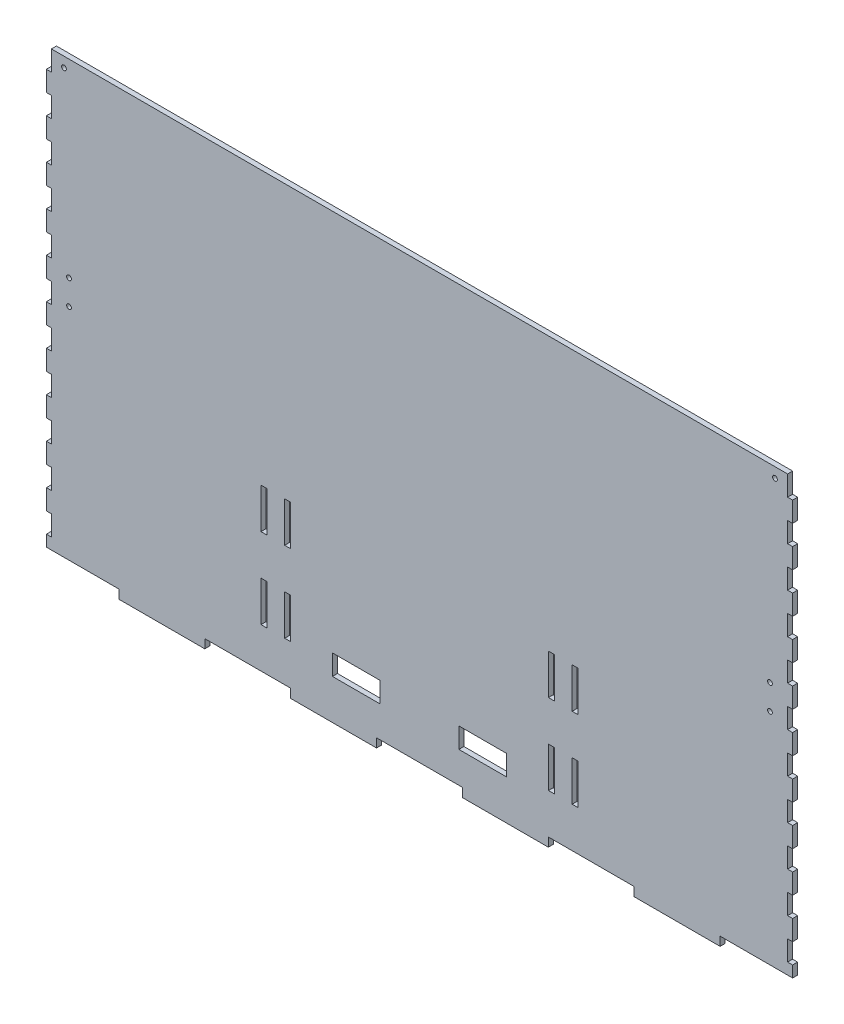
SolidWorks part; units mm, degrees
ref_plane "Front Plane" through (0, 0, 0) normal (0, 0, 1) x (1, 0, 0)
ref_plane "Top Plane" through (0, 0, 0) normal (0, 1, 0) x (1, 0, 0)
ref_plane "Right Plane" through (0, 0, 0) normal (1, 0, 0) x (0, 0, -1)
sketch "Sketch1" plane through (0, 0, 0) normal (0, 0, 1) x (1, 0, 0)
  line L0 (0, 139.7) -> (0, -139.7) construction
  line L1 (-406.4, 139.7) -> (406.4, 139.7)
  line L2 (-406.4, 139.7) -> (-406.4, -139.7)
  line L3 (-406.4, -139.7) -> (406.4, -139.7)
  line L4 (406.4, 139.7) -> (406.4, -139.7)
  line L49 (-381, 127) -> (-381, 114.3)
  line L54 (-381, 139.7) -> (-377.825, 139.7)
  line L55 (-381, 139.7) -> (-381, 127)
  line L56 (-381, 127) -> (-377.825, 127)
  line L57 (-377.825, 139.7) -> (-377.825, 127)
  line L58 (-381, 127) -> (-377.825, 127)
  line L59 (-377.825, 127) -> (-377.825, 114.3)
  line L60 (-381, 114.3) -> (-377.825, 114.3)
  line L61 (-381, 114.3) -> (-381, 101.6)
  line L62 (-381, 114.3) -> (-377.825, 114.3)
  line L63 (-377.825, 114.3) -> (-377.825, 101.6)
  line L64 (-381, 101.6) -> (-377.825, 101.6)
  line L65 (-381, 101.6) -> (-381, 88.9)
  line L66 (-381, 101.6) -> (-377.825, 101.6)
  line L67 (-377.825, 101.6) -> (-377.825, 88.9)
  line L68 (-381, 88.9) -> (-377.825, 88.9)
  line L69 (-381, 88.9) -> (-381, 76.2)
  line L70 (-381, 88.9) -> (-377.825, 88.9)
  line L71 (-377.825, 88.9) -> (-377.825, 76.2)
  line L72 (-381, 76.2) -> (-377.825, 76.2)
  line L73 (-381, 76.2) -> (-381, 63.5)
  line L74 (-381, 76.2) -> (-377.825, 76.2)
  line L75 (-377.825, 76.2) -> (-377.825, 63.5)
  line L76 (-381, 63.5) -> (-377.825, 63.5)
  line L77 (-381, 63.5) -> (-381, 50.8)
  line L78 (-381, 63.5) -> (-377.825, 63.5)
  line L79 (-377.825, 63.5) -> (-377.825, 50.8)
  line L80 (-381, 50.8) -> (-377.825, 50.8)
  line L81 (-381, 50.8) -> (-381, 38.1)
  line L82 (-381, 50.8) -> (-377.825, 50.8)
  line L83 (-377.825, 50.8) -> (-377.825, 38.1)
  line L84 (-381, 38.1) -> (-377.825, 38.1)
  line L85 (-381, 38.1) -> (-381, 25.4)
  line L86 (-381, 38.1) -> (-377.825, 38.1)
  line L87 (-377.825, 38.1) -> (-377.825, 25.4)
  line L88 (-381, 25.4) -> (-377.825, 25.4)
  line L89 (377.825, 127) -> (377.825, 114.3)
  line L90 (377.825, 139.7) -> (381, 139.7)
  line L91 (377.825, 139.7) -> (377.825, 127)
  line L92 (377.825, 127) -> (381, 127)
  line L93 (381, 139.7) -> (381, 127)
  line L94 (377.825, 127) -> (381, 127)
  line L95 (381, 127) -> (381, 114.3)
  line L96 (377.825, 114.3) -> (381, 114.3)
  line L97 (377.825, 114.3) -> (377.825, 101.6)
  line L98 (377.825, 114.3) -> (381, 114.3)
  line L99 (381, 114.3) -> (381, 101.6)
  line L100 (377.825, 101.6) -> (381, 101.6)
  line L101 (377.825, 101.6) -> (377.825, 88.9)
  line L102 (377.825, 101.6) -> (381, 101.6)
  line L103 (381, 101.6) -> (381, 88.9)
  line L104 (377.825, 88.9) -> (381, 88.9)
  line L105 (377.825, 88.9) -> (377.825, 76.2)
  line L106 (377.825, 88.9) -> (381, 88.9)
  line L107 (381, 88.9) -> (381, 76.2)
  line L108 (377.825, 76.2) -> (381, 76.2)
  line L109 (377.825, 76.2) -> (377.825, 63.5)
  line L110 (377.825, 76.2) -> (381, 76.2)
  line L111 (381, 76.2) -> (381, 63.5)
  line L112 (377.825, 63.5) -> (381, 63.5)
  line L113 (377.825, 63.5) -> (377.825, 50.8)
  line L114 (377.825, 63.5) -> (381, 63.5)
  line L115 (381, 63.5) -> (381, 50.8)
  line L116 (377.825, 50.8) -> (381, 50.8)
  line L117 (377.825, 50.8) -> (377.825, 38.1)
  line L118 (377.825, 50.8) -> (381, 50.8)
  line L119 (381, 50.8) -> (381, 38.1)
  line L120 (377.825, 38.1) -> (381, 38.1)
  line L121 (377.825, 38.1) -> (377.825, 25.4)
  line L122 (377.825, 38.1) -> (381, 38.1)
  line L123 (381, 38.1) -> (381, 25.4)
  line L124 (377.825, 25.4) -> (381, 25.4)
  line L125 (-352.2133, -134.112) -> (-352.2133, -139.7)
  line L126 (-406.4, -134.112) -> (-352.2133, -134.112)
  line L127 (-406.4, -134.112) -> (-406.4, -139.7)
  line L128 (-406.4, -139.7) -> (-352.2133, -139.7)
  line L129 (-352.2133, -134.112) -> (-352.2133, -139.7)
  line L130 (-352.2133, -134.112) -> (-298.0267, -134.112)
  line L131 (-298.0267, -134.112) -> (-298.0267, -139.7)
  line L132 (-352.2133, -139.7) -> (-298.0267, -139.7)
  line L133 (-298.0267, -134.112) -> (-298.0267, -139.7)
  line L134 (-298.0267, -134.112) -> (-243.84, -134.112)
  line L135 (-243.84, -134.112) -> (-243.84, -139.7)
  line L136 (-298.0267, -139.7) -> (-243.84, -139.7)
  line L137 (-243.84, -134.112) -> (-243.84, -139.7)
  line L138 (-243.84, -134.112) -> (-189.6533, -134.112)
  line L139 (-189.6533, -134.112) -> (-189.6533, -139.7)
  line L140 (-243.84, -139.7) -> (-189.6533, -139.7)
  line L141 (-189.6533, -134.112) -> (-189.6533, -139.7)
  line L142 (-189.6533, -134.112) -> (-135.4667, -134.112)
  line L143 (-135.4667, -134.112) -> (-135.4667, -139.7)
  line L144 (-189.6533, -139.7) -> (-135.4667, -139.7)
  line L145 (-135.4667, -134.112) -> (-135.4667, -139.7)
  line L146 (-135.4667, -134.112) -> (-81.28, -134.112)
  line L147 (-81.28, -134.112) -> (-81.28, -139.7)
  line L148 (-135.4667, -139.7) -> (-81.28, -139.7)
  line L149 (-81.28, -134.112) -> (-81.28, -139.7)
  line L150 (-81.28, -134.112) -> (-27.0933, -134.112)
  line L151 (-27.0933, -134.112) -> (-27.0933, -139.7)
  line L152 (-81.28, -139.7) -> (-27.0933, -139.7)
  line L153 (-27.0933, -134.112) -> (-27.0933, -139.7)
  line L154 (-27.0933, -134.112) -> (27.0933, -134.112)
  line L155 (27.0933, -134.112) -> (27.0933, -139.7)
  line L156 (-27.0933, -139.7) -> (27.0933, -139.7)
  line L157 (27.0933, -134.112) -> (27.0933, -139.7)
  line L158 (27.0933, -134.112) -> (81.28, -134.112)
  line L159 (81.28, -134.112) -> (81.28, -139.7)
  line L160 (27.0933, -139.7) -> (81.28, -139.7)
  line L161 (81.28, -134.112) -> (81.28, -139.7)
  line L162 (81.28, -134.112) -> (135.4667, -134.112)
  line L163 (135.4667, -134.112) -> (135.4667, -139.7)
  line L164 (81.28, -139.7) -> (135.4667, -139.7)
  line L165 (135.4667, -134.112) -> (135.4667, -139.7)
  line L166 (135.4667, -134.112) -> (189.6533, -134.112)
  line L167 (189.6533, -134.112) -> (189.6533, -139.7)
  line L168 (135.4667, -139.7) -> (189.6533, -139.7)
  line L169 (189.6533, -134.112) -> (189.6533, -139.7)
  line L170 (189.6533, -134.112) -> (243.84, -134.112)
  line L171 (243.84, -134.112) -> (243.84, -139.7)
  line L172 (189.6533, -139.7) -> (243.84, -139.7)
  line L173 (243.84, -134.112) -> (243.84, -139.7)
  line L174 (243.84, -134.112) -> (298.0267, -134.112)
  line L175 (298.0267, -134.112) -> (298.0267, -139.7)
  line L176 (243.84, -139.7) -> (298.0267, -139.7)
  line L177 (298.0267, -134.112) -> (298.0267, -139.7)
  line L178 (298.0267, -134.112) -> (352.2133, -134.112)
  line L179 (352.2133, -134.112) -> (352.2133, -139.7)
  line L180 (298.0267, -139.7) -> (352.2133, -139.7)
  line L181 (352.2133, -134.112) -> (352.2133, -139.7)
  line L182 (352.2133, -134.112) -> (406.4, -134.112)
  line L183 (406.4, -134.112) -> (406.4, -139.7)
  line L184 (352.2133, -139.7) -> (406.4, -139.7)
  line L205 (-90.678, 84.5227) -> (-90.678, -139.7) construction
  line L206 (90.678, 84.5227) -> (90.678, -139.7) construction
  line L207 (-90.678, -27.5886) -> (90.678, -27.5886) construction
  line L208 (-381, 25.4) -> (-381, 12.7)
  line L209 (-381, 25.4) -> (-377.825, 25.4)
  line L210 (-377.825, 25.4) -> (-377.825, 12.7)
  line L211 (-381, 12.7) -> (-377.825, 12.7)
  line L212 (-381, 12.7) -> (-381, 0)
  line L213 (-381, 12.7) -> (-377.825, 12.7)
  line L214 (-377.825, 12.7) -> (-377.825, 0)
  line L215 (-381, 0) -> (-377.825, 0)
  line L224 (-377.825, 0) -> (377.825, 0) construction
  line L229 (377.825, 25.4) -> (377.825, 12.7)
  line L230 (377.825, 25.4) -> (381, 25.4)
  line L231 (381, 25.4) -> (381, 12.7)
  line L232 (377.825, 12.7) -> (381, 12.7)
  line L233 (377.825, 12.7) -> (377.825, 0)
  line L234 (377.825, 12.7) -> (381, 12.7)
  line L235 (381, 12.7) -> (381, 0)
  line L236 (377.825, 0) -> (381, 0)
  line L237 (-381, 0) -> (-381, -12.7)
  line L238 (-381, 0) -> (-377.825, 0)
  line L239 (-377.825, 0) -> (-377.825, -12.7)
  line L240 (-381, -12.7) -> (-377.825, -12.7)
  line L241 (-381, -12.7) -> (-381, -25.4)
  line L242 (-381, -12.7) -> (-377.825, -12.7)
  line L243 (-377.825, -12.7) -> (-377.825, -25.4)
  line L244 (-381, -25.4) -> (-377.825, -25.4)
  line L245 (-381, -25.4) -> (-381, -38.1)
  line L246 (-381, -25.4) -> (-377.825, -25.4)
  line L247 (-377.825, -25.4) -> (-377.825, -38.1)
  line L248 (-381, -38.1) -> (-377.825, -38.1)
  line L249 (-381, -38.1) -> (-381, -50.8)
  line L250 (-381, -38.1) -> (-377.825, -38.1)
  line L251 (-377.825, -38.1) -> (-377.825, -50.8)
  line L252 (-381, -50.8) -> (-377.825, -50.8)
  line L253 (-381, -50.8) -> (-381, -63.5)
  line L254 (-381, -50.8) -> (-377.825, -50.8)
  line L255 (-377.825, -50.8) -> (-377.825, -63.5)
  line L256 (-381, -63.5) -> (-377.825, -63.5)
  line L257 (-381, -63.5) -> (-381, -76.2)
  line L258 (-381, -63.5) -> (-377.825, -63.5)
  line L259 (-377.825, -63.5) -> (-377.825, -76.2)
  line L260 (-381, -76.2) -> (-377.825, -76.2)
  line L261 (-381, -76.2) -> (-381, -88.9)
  line L262 (-381, -76.2) -> (-377.825, -76.2)
  line L263 (-377.825, -76.2) -> (-377.825, -88.9)
  line L264 (-381, -88.9) -> (-377.825, -88.9)
  line L265 (-381, -88.9) -> (-381, -101.6)
  line L266 (-381, -88.9) -> (-377.825, -88.9)
  line L267 (-377.825, -88.9) -> (-377.825, -101.6)
  line L268 (-381, -101.6) -> (-377.825, -101.6)
  line L269 (-381, -101.6) -> (-381, -114.3)
  line L270 (-381, -101.6) -> (-377.825, -101.6)
  line L271 (-377.825, -101.6) -> (-377.825, -114.3)
  line L272 (-381, -114.3) -> (-377.825, -114.3)
  line L273 (-381, -114.3) -> (-381, -127)
  line L274 (-381, -114.3) -> (-377.825, -114.3)
  line L275 (-377.825, -114.3) -> (-377.825, -127)
  line L276 (-381, -127) -> (-377.825, -127)
  line L277 (-381, -127) -> (-381, -139.7)
  line L278 (-381, -127) -> (-377.825, -127)
  line L279 (-377.825, -127) -> (-377.825, -139.7)
  line L280 (-381, -139.7) -> (-377.825, -139.7)
  line L281 (377.825, 0) -> (377.825, -12.7)
  line L282 (377.825, 0) -> (381, 0)
  line L283 (381, 0) -> (381, -12.7)
  line L284 (377.825, -12.7) -> (381, -12.7)
  line L285 (377.825, -12.7) -> (377.825, -25.4)
  line L286 (377.825, -12.7) -> (381, -12.7)
  line L287 (381, -12.7) -> (381, -25.4)
  line L288 (377.825, -25.4) -> (381, -25.4)
  line L289 (377.825, -25.4) -> (377.825, -38.1)
  line L290 (377.825, -25.4) -> (381, -25.4)
  line L291 (381, -25.4) -> (381, -38.1)
  line L292 (377.825, -38.1) -> (381, -38.1)
  line L293 (377.825, -38.1) -> (377.825, -50.8)
  line L294 (377.825, -38.1) -> (381, -38.1)
  line L295 (381, -38.1) -> (381, -50.8)
  line L296 (377.825, -50.8) -> (381, -50.8)
  line L297 (377.825, -50.8) -> (377.825, -63.5)
  line L298 (377.825, -50.8) -> (381, -50.8)
  line L299 (381, -50.8) -> (381, -63.5)
  line L300 (377.825, -63.5) -> (381, -63.5)
  line L301 (377.825, -63.5) -> (377.825, -76.2)
  line L302 (377.825, -63.5) -> (381, -63.5)
  line L303 (381, -63.5) -> (381, -76.2)
  line L304 (377.825, -76.2) -> (381, -76.2)
  line L305 (377.825, -76.2) -> (377.825, -88.9)
  line L306 (377.825, -76.2) -> (381, -76.2)
  line L307 (381, -76.2) -> (381, -88.9)
  line L308 (377.825, -88.9) -> (381, -88.9)
  line L309 (377.825, -88.9) -> (377.825, -101.6)
  line L310 (377.825, -88.9) -> (381, -88.9)
  line L311 (381, -88.9) -> (381, -101.6)
  line L312 (377.825, -101.6) -> (381, -101.6)
  line L313 (377.825, -101.6) -> (377.825, -114.3)
  line L314 (377.825, -101.6) -> (381, -101.6)
  line L315 (381, -101.6) -> (381, -114.3)
  line L316 (377.825, -114.3) -> (381, -114.3)
  line L317 (377.825, -114.3) -> (377.825, -127)
  line L318 (377.825, -114.3) -> (381, -114.3)
  line L319 (381, -114.3) -> (381, -127)
  line L320 (377.825, -127) -> (381, -127)
  line L321 (377.825, -127) -> (377.825, -139.7)
  line L322 (377.825, -127) -> (381, -127)
  line L323 (381, -127) -> (381, -139.7)
  line L324 (377.825, -139.7) -> (381, -139.7)
  point P6 (0, 0)
  point P128 (0, -27.5886)
  point P153 (0, 0)
  dimension "D4" = 12.7
  dimension "D5" = 3.175
  dimension "D10" = 181.356
  dimension "D12" = 755.65
  dimension "D8" = 812.8
  dimension "D11" = 54.1867
  dimension "D2" = 273.812
  dimension "D9" = 279.4
  dimension "D3" = 22
  dimension "D7" = 15
  dimension "D6" = 22
extrude "Main Extrude" add sketch "Sketch1" along normal blind 3.175 contours L321 L317 L313 L309 L305 L301 L297 L293 L289 L285 L281 L233 L229 L121 L117 L113 L109 L105 L101 L97 L89 L91 L1 L57 L59 L63 L67 L71 L75 L79 L83 L87 L210 L214 L239 L243 L247 L251 L255 L259 L263 L267 L271 L275 L279 L126 L130 L134 L138 L142 L146 | L277 L273 L269 L265 L261 L257 L253 L249 L245 L241 L237 L212 L208 L85 L81 L77 L73 L69 L65 L61 L49 L55 L1 L2 L126 | L319 L323 L182 L4 L1 L93 L95 L99 L103 L107 L111 L115 L119 L123 L231 L235 L283 L287 L291 L295 L299 L303 L307 L311 L315 | L126 L279 L3 L125 | L135 L134 L131 L3 | L143 L142 L139 L3 | L151 L150 L147 L3 | L159 L158 L155 L3 | L167 L166 L163 L3 | L175 L174 L171 L3 | L323 L182 L321 L184 | L89 L96 L95 L92 | L101 L104 L103 L100 | L109 L112 L111 L108 | L117 L120 L119 L116 | L229 L232 L231 L124 | L281 L284 L283 L236 | L289 L292 L291 L288 | L297 L300 L299 L296 | L305 L308 L307 L304 | L313 L316 L315 L312 | L323 L320 L321 L182 | L49 L60 L59 L56 | L65 L68 L67 L64 | L73 L76 L75 L72 | L81 L84 L83 L80 | L208 L211 L210 L88 | L237 L240 L239 L215 | L245 L248 L247 L244 | L253 L256 L255 L252 | L261 L264 L263 L260 | L269 L272 L271 L268 | L279 L276 L277 L126 | L277 L126 L2 L3 | L321 L182 L179 L3 | L182 L323 L3 L4 | L279 L126 L277 L128 region at (-393.7, 2.794, 0) region at (-393.7, -136.906, 0) region at (0, 2.794, 0) region at (-379.4125, 120.65, 0) region at (-379.4125, -130.556, 0) region at (-379.4125, -136.906, 0) region at (-365.0192, -136.906, 0) region at (393.7, 2.794, 0) region at (379.4125, 120.65, 0) region at (-379.4125, 95.25, 0) region at (-379.4125, -107.95, 0) region at (-270.9333, -136.906, 0) region at (393.7, -136.906, 0) region at (379.4125, 95.25, 0) region at (-379.4125, 69.85, 0) region at (-379.4125, -82.55, 0) region at (379.4125, -136.906, 0) region at (379.4125, -130.556, 0) region at (-162.56, -136.906, 0) region at (365.0192, -136.906, 0) region at (379.4125, 69.85, 0) region at (-379.4125, 44.45, 0) region at (-379.4125, -57.15, 0) region at (379.4125, -107.95, 0) region at (-54.1867, -136.906, 0) region at (270.9333, -136.906, 0) region at (379.4125, 44.45, 0) region at (-379.4125, 19.05, 0) region at (-379.4125, -31.75, 0) region at (379.4125, -82.55, 0) region at (54.1867, -136.906, 0) region at (162.56, -136.906, 0) region at (379.4125, 19.05, 0) region at (-379.4125, -6.35, 0) region at (379.4125, -57.15, 0) region at (379.4125, -6.35, 0) region at (379.4125, -31.75, 0)
sketch "Sketch8" plane through (0, 0, 3.175) normal (0, 0, 1) x (1, 0, 0)
  line L0 (-406.4, 139.7) -> (-406.4, -139.7) construction
  line L1 (-381, 28.2575) -> (-384.175, 28.2575)
  line L2 (-381, 28.2575) -> (-381, -3.6195)
  line L3 (-381, -3.6195) -> (-384.175, -3.6195)
  line L4 (-384.175, 28.2575) -> (-384.175, -3.6195)
  line L5 (-406.4, -139.7) -> (-352.2133, -139.7) construction
  line L6 (381, 28.2575) -> (384.175, 28.2575)
  line L7 (381, 28.2575) -> (381, -3.6195)
  line L8 (381, -3.6195) -> (384.175, -3.6195)
  line L9 (384.175, 28.2575) -> (384.175, -3.6195)
  line L11 (-381, 88.9) -> (-381, 76.2) construction
  line L12 (-352.2133, -134.112) -> (-298.0267, -134.112) construction
  line L13 (381, 88.9) -> (381, 76.2) construction
  line L14 (-393.7, -120.65) -> (393.7, -120.65) construction
  circle A0 centre (-393.7, -120.65) radius 1.5
  circle A1 centre (393.7, -120.65) radius 1.5
  point P6 (0, -120.65)
  point P16 (-384.175, 12.319)
  dimension "D5" = 3
  dimension "D1" = 31.877
  dimension "D2" = 3.175
  dimension "D3" = 146.431
  dimension "D4" = 19.05
  dimension "D6" = 12.7
extrude "Mount Holes" cut sketch "Sketch8" against normal through all
sketch "Sketch3" plane through (0, 0, 3.175) normal (0, 0, 1) x (1, 0, 0)
  line L0 (-135.4667, -134.112) -> (-81.28, -134.112) construction
  line L1 (-96.52, 126.492) -> (-84.836, 126.492)
  line L2 (-96.52, 126.492) -> (-96.52, -134.112)
  line L3 (-96.52, -134.112) -> (-84.836, -134.112)
  line L4 (-84.836, 126.492) -> (-84.836, -134.112)
  line L5 (81.28, -134.112) -> (135.4667, -134.112) construction
  line L6 (84.836, 126.492) -> (96.52, 126.492)
  line L7 (84.836, 126.492) -> (84.836, -134.112)
  line L8 (84.836, -134.112) -> (96.52, -134.112)
  line L9 (96.52, 126.492) -> (96.52, -134.112)
  line L10 (-84.836, -3.81) -> (84.836, -3.81) construction
  line L12 (-106.553, 10.3505) -> (-74.803, 10.3505)
  line L13 (-106.553, 10.3505) -> (-106.553, 0.8255)
  line L14 (-106.553, 0.8255) -> (-74.803, 0.8255)
  line L15 (-74.803, 10.3505) -> (-74.803, 0.8255)
  line L16 (74.803, 10.3505) -> (106.553, 10.3505)
  line L17 (74.803, 10.3505) -> (74.803, 0.8255)
  line L18 (74.803, 0.8255) -> (106.553, 0.8255)
  line L19 (106.553, 10.3505) -> (106.553, 0.8255)
  line L20 (-96.52, 126.492) -> (-92.6465, 126.492)
  line L21 (-96.52, 126.492) -> (-96.52, 82.042)
  line L22 (-96.52, 82.042) -> (-92.6465, 82.042)
  line L23 (-92.6465, 126.492) -> (-92.6465, 82.042)
  line L24 (-84.836, 126.492) -> (-88.7095, 126.492)
  line L25 (-84.836, 126.492) -> (-84.836, 82.042)
  line L26 (-84.836, 82.042) -> (-88.7095, 82.042)
  line L27 (-88.7095, 126.492) -> (-88.7095, 82.042)
  line L28 (84.836, 126.492) -> (88.7095, 126.492)
  line L29 (84.836, 126.492) -> (84.836, 82.042)
  line L30 (84.836, 82.042) -> (88.7095, 82.042)
  line L31 (88.7095, 126.492) -> (88.7095, 82.042)
  line L32 (96.52, 126.492) -> (92.6465, 126.492)
  line L33 (96.52, 126.492) -> (96.52, 82.042)
  line L34 (96.52, 82.042) -> (92.6465, 82.042)
  line L35 (92.6465, 126.492) -> (92.6465, 82.042)
  point P14 (-90.678, 126.492)
  point P15 (90.678, 126.492)
  point P16 (0, -3.81)
  point P27 (-90.678, 10.3505)
  point P28 (90.678, 10.3505)
  point P29 (-74.803, 5.588)
  dimension "D1" = 11.684
  dimension "D2" = 260.604
  dimension "D3" = 181.356
  dimension "D4" = 9.525
  dimension "D5" = 139.7
  dimension "D6" = 31.75
  dimension "D8" = 3.937
  dimension "D7" = 44.45
extrude "Door Slots" [suppressed] cut sketch "Sketch3" against normal through all contours L2 L12 L4 L1 | L2 L14 L4 L12 | L15 L12 L4 L14 | L13 L14 L2 L12 | L14 L2 L3 L4 | L7 L16 L9 L6 | L7 L18 L9 L16 | L19 L16 L9 L18 | L17 L18 L7 L16 | L18 L7 L8 L9
sketch "Sketch4" plane through (0, 0, 0) normal (0, 0, 1) x (1, 0, 0)
  line L1 (-81.28, -139.7) -> (-27.0933, -139.7) construction
  line L2 (-55.88, -112.41) -> (-52.578, -112.41)
  line L3 (-52.578, -112.41) -> (-52.578, -106.172)
  line L4 (-52.578, -106.172) -> (-1.778, -106.172)
  line L5 (-1.778, -106.172) -> (-1.778, -112.41)
  line L6 (-1.778, -112.41) -> (1.524, -112.41)
  line L9 (-55.88, -112.41) -> (-55.88, -134.112)
  line L10 (-55.88, -134.112) -> (-52.578, -134.112)
  line L11 (-52.578, -134.112) -> (-52.578, -139.7)
  line L12 (1.524, -112.41) -> (1.524, -134.112)
  line L13 (1.524, -134.112) -> (-1.778, -134.112)
  line L14 (-1.778, -134.112) -> (-1.778, -139.7)
  line L15 (-52.578, -139.7) -> (-1.778, -139.7)
  line L16 (-27.0933, -134.112) -> (27.0933, -134.112) construction
  line L17 (-27.0933, -134.112) -> (27.0933, -134.112) construction
  line L18 (12.128, -101.642) -> (42.228, -101.642)
  line L19 (12.128, -101.642) -> (12.128, -114.492)
  line L20 (12.128, -114.492) -> (42.228, -114.492)
  line L21 (42.228, -101.642) -> (42.228, -114.492)
  line L24 (-96.52, -134.112) -> (-84.836, -134.112) construction
  line L25 (84.836, -134.112) -> (96.52, -134.112) construction
  point P9 (-27.178, -106.172)
  point P10 (-27.178, -139.7)
  point P22 (27.178, -114.492)
  point P25 (90.678, -134.112)
  point P26 (12.128, -108.067)
  point P30 (-90.678, -134.112)
  dimension "D1" = 50.8
  dimension "D2" = 3.302
  dimension "D4" = 21.702
  dimension "D5" = 30.1
  dimension "D6" = 12.85
  dimension "D9" = 63.5
  dimension "D8" = 63.5
  dimension "D3" = 27.94
  dimension "D7" = 26.045
extrude "Trough and Lever Holes" [suppressed] cut sketch "Sketch4" along normal through all contours L11 L15 L14 L13 L12 L6 L5 L4 L3 L2 L9 L10 | L21 L18 L19 L20
sketch "Sketch5" plane through (0, 0, 3.175) normal (0, 0, 1) x (1, 0, 0)
  line L0 (-90.678, 126.492) -> (-90.678, -134.112) construction
  line L1 (-96.52, 126.492) -> (-84.836, 126.492) construction
  line L2 (-96.52, -134.112) -> (-84.836, -134.112) construction
  line L3 (90.678, 126.492) -> (90.678, -134.112) construction
  line L4 (84.836, 126.492) -> (96.52, 126.492) construction
  line L5 (84.836, -134.112) -> (96.52, -134.112) construction
  line L6 (-135.4667, -134.112) -> (-81.28, -134.112) construction
  line L19 (-99.998, -134.112) -> (-96.3199, -134.112)
  line L20 (-99.998, -134.112) -> (-99.998, -108.712)
  line L21 (-99.998, -108.712) -> (-96.3199, -108.712)
  line L22 (-96.3199, -134.112) -> (-96.3199, -108.712)
  line L24 (-99.998, -108.712) -> (-96.3199, -108.712)
  line L25 (-99.998, -108.712) -> (-99.998, -83.312)
  line L26 (-99.998, -83.312) -> (-96.3199, -83.312)
  line L27 (-96.3199, -108.712) -> (-96.3199, -83.312)
  line L28 (-96.3199, -83.312) -> (-99.998, -83.312)
  line L29 (-96.3199, -83.312) -> (-96.3199, -57.912)
  line L30 (-96.3199, -57.912) -> (-99.998, -57.912)
  line L31 (-99.998, -83.312) -> (-99.998, -57.912)
  line L32 (-99.998, -57.912) -> (-96.3199, -57.912)
  line L33 (-99.998, -57.912) -> (-99.998, -32.512)
  line L34 (-99.998, -32.512) -> (-96.3199, -32.512)
  line L35 (-96.3199, -57.912) -> (-96.3199, -32.512)
  line L36 (-96.3199, -32.512) -> (-99.998, -32.512)
  line L37 (-96.3199, -32.512) -> (-96.3199, -7.112)
  line L38 (-96.3199, -7.112) -> (-99.998, -7.112)
  line L39 (-99.998, -32.512) -> (-99.998, -7.112)
  line L40 (-81.358, -108.712) -> (-85.0361, -108.712)
  line L41 (-85.0361, -134.112) -> (-85.0361, -108.712)
  line L42 (-81.358, -134.112) -> (-85.0361, -134.112)
  line L43 (-81.358, -134.112) -> (-81.358, -108.712)
  line L44 (-81.358, -83.312) -> (-85.0361, -83.312)
  line L45 (-85.0361, -108.712) -> (-85.0361, -83.312)
  line L46 (-81.358, -108.712) -> (-85.0361, -108.712)
  line L47 (-81.358, -108.712) -> (-81.358, -83.312)
  line L48 (-85.0361, -57.912) -> (-81.358, -57.912)
  line L49 (-81.358, -83.312) -> (-81.358, -57.912)
  line L50 (-85.0361, -83.312) -> (-81.358, -83.312)
  line L51 (-85.0361, -83.312) -> (-85.0361, -57.912)
  line L52 (-81.358, -32.512) -> (-85.0361, -32.512)
  line L53 (-85.0361, -57.912) -> (-85.0361, -32.512)
  line L54 (-81.358, -57.912) -> (-85.0361, -57.912)
  line L55 (-81.358, -57.912) -> (-81.358, -32.512)
  line L56 (-85.0361, -7.112) -> (-81.358, -7.112)
  line L57 (-81.358, -32.512) -> (-81.358, -7.112)
  line L58 (-85.0361, -32.512) -> (-81.358, -32.512)
  line L59 (-85.0361, -32.512) -> (-85.0361, -7.112)
  line L60 (0, -1.7463) -> (0, 1.7463) construction
  line L61 (99.998, -108.712) -> (96.3199, -108.712)
  line L62 (96.3199, -134.112) -> (96.3199, -108.712)
  line L63 (99.998, -134.112) -> (96.3199, -134.112)
  line L64 (99.998, -134.112) -> (99.998, -108.712)
  line L65 (99.998, -83.312) -> (96.3199, -83.312)
  line L66 (96.3199, -108.712) -> (96.3199, -83.312)
  line L67 (99.998, -108.712) -> (96.3199, -108.712)
  line L68 (99.998, -108.712) -> (99.998, -83.312)
  line L69 (96.3199, -57.912) -> (99.998, -57.912)
  line L70 (99.998, -83.312) -> (99.998, -57.912)
  line L71 (96.3199, -83.312) -> (99.998, -83.312)
  line L72 (96.3199, -83.312) -> (96.3199, -57.912)
  line L73 (99.998, -32.512) -> (96.3199, -32.512)
  line L74 (96.3199, -57.912) -> (96.3199, -32.512)
  line L75 (99.998, -57.912) -> (96.3199, -57.912)
  line L76 (99.998, -57.912) -> (99.998, -32.512)
  line L77 (96.3199, -7.112) -> (99.998, -7.112)
  line L78 (99.998, -32.512) -> (99.998, -7.112)
  line L79 (96.3199, -32.512) -> (99.998, -32.512)
  line L80 (96.3199, -32.512) -> (96.3199, -7.112)
  line L81 (85.0361, -32.512) -> (85.0361, -7.112)
  line L82 (85.0361, -32.512) -> (81.358, -32.512)
  line L83 (81.358, -32.512) -> (81.358, -7.112)
  line L84 (85.0361, -7.112) -> (81.358, -7.112)
  line L85 (81.358, -57.912) -> (81.358, -32.512)
  line L86 (81.358, -57.912) -> (85.0361, -57.912)
  line L87 (85.0361, -57.912) -> (85.0361, -32.512)
  line L88 (81.358, -32.512) -> (85.0361, -32.512)
  line L89 (85.0361, -83.312) -> (85.0361, -57.912)
  line L90 (85.0361, -83.312) -> (81.358, -83.312)
  line L91 (81.358, -83.312) -> (81.358, -57.912)
  line L92 (85.0361, -57.912) -> (81.358, -57.912)
  line L93 (81.358, -108.712) -> (81.358, -83.312)
  line L94 (81.358, -108.712) -> (85.0361, -108.712)
  line L95 (85.0361, -108.712) -> (85.0361, -83.312)
  line L96 (81.358, -83.312) -> (85.0361, -83.312)
  line L97 (81.358, -134.112) -> (81.358, -108.712)
  line L98 (81.358, -134.112) -> (85.0361, -134.112)
  line L99 (85.0361, -134.112) -> (85.0361, -108.712)
  line L100 (81.358, -108.712) -> (85.0361, -108.712)
  dimension "D1" = 25.4
  dimension "D3" = 5.6419
  dimension "D2" = 9.32
extrude "Door Guide Slots" cut sketch "Sketch5" against normal through all contours L21 L27 L26 L25 | L30 L35 L34 L33 | L48 L55 L52 L53 | L40 L47 L44 L45 | L86 L87 L82 L85 | L94 L95 L90 L93 | L69 L76 L73 L74 | L61 L68 L65 L66 region at (-98.1589, -96.012, 3.175) region at (-98.1589, -45.212, 3.175) region at (-83.1971, -96.012, 3.175) region at (-83.1971, -45.212, 3.175) region at (98.1589, -96.012, 3.175) region at (98.1589, -45.212, 3.175) region at (83.1971, -45.212, 3.175) region at (83.1971, -96.012, 3.175)
sketch "Sketch7" plane through (0, 0, 3.175) normal (0, 0, 1) x (1, 0, 0)
  line L0 (-24.828, -108.067) -> (24.828, -108.067) construction
  line L1 (-54.928, -101.642) -> (-24.828, -101.642)
  line L2 (-54.928, -101.642) -> (-54.928, -114.492)
  line L3 (-54.928, -114.492) -> (-24.828, -114.492)
  line L4 (-24.828, -101.642) -> (-24.828, -114.492)
  line L5 (54.928, -101.642) -> (24.828, -101.642)
  line L6 (54.928, -101.642) -> (54.928, -114.492)
  line L7 (54.928, -114.492) -> (24.828, -114.492)
  line L8 (24.828, -101.642) -> (24.828, -114.492)
  line L9 (0, -108.067) -> (0, 0) construction
  line L10 (-96.52, -134.112) -> (-84.836, -134.112) construction
  line L12 (-135.4667, -134.112) -> (-81.28, -134.112) construction
  point P12 (-54.928, -108.067)
  point P15 (-39.878, -101.642)
  point P18 (-90.678, -134.112)
  dimension "D1" = 12.85
  dimension "D2" = 30.1
  dimension "D3" = 50.8
  dimension "D4" = 26.045
extrude "Lever Holes" cut sketch "Sketch7" against normal through all
sketch "Sketch10" [suppressed] plane through (0, 0, 3.175) normal (0, 0, 1) x (1, 0, 0)
  line L0 (-101.678, 127.492) -> (-79.678, 127.492) construction
  line L2 (-92.6465, 126.492) -> (-88.7095, 126.492) construction
  line L3 (-90.678, 127.492) -> (-90.678, 126.492) construction
  line L4 (79.678, 127.492) -> (101.678, 127.492) construction
  line L5 (90.678, 127.492) -> (90.678, 126.492) construction
  line L6 (88.7095, 126.492) -> (92.6465, 126.492) construction
  circle A0 centre (-101.678, 127.492) radius 1.5
  circle A1 centre (-79.678, 127.492) radius 1.5
  circle A2 centre (79.678, 127.492) radius 1.5
  circle A3 centre (101.678, 127.492) radius 1.5
  dimension "D1" = 3
  dimension "D2" = 22
  dimension "D3" = 1
extrude "Door Guide Mount Holes" [suppressed] cut sketch "Sketch10" against normal through all
sketch "Sketch12" plane through (0, 0, 3.175) normal (0, 0, 1) x (1, 0, 0)
  line L0 (-246.507, 20.193) -> (-246.507, 4.445) construction
  line L1 (-221.107, 20.193) -> (-221.107, 4.445) construction
  line L2 (-246.507, 20.193) -> (-221.107, 20.193) construction
  line L3 (-246.507, 4.445) -> (-221.107, 4.445) construction
  line L4 (-243.332, 133.35) -> (-224.282, 133.35) construction
  line L5 (-406.4, 139.7) -> (406.4, 139.7) construction
  line L6 (-233.807, 20.193) -> (-233.807, 133.35) construction
  line L7 (-243.84, -134.112) -> (-189.6533, -134.112) construction
  line L8 (0, -1.7463) -> (0, 1.7463) construction
  line L9 (233.807, 20.193) -> (233.807, 133.35) construction
  line L10 (243.332, 133.35) -> (224.282, 133.35) construction
  line L11 (246.507, 4.445) -> (221.107, 4.445) construction
  line L12 (246.507, 20.193) -> (221.107, 20.193) construction
  line L13 (221.107, 20.193) -> (221.107, 4.445) construction
  line L14 (246.507, 20.193) -> (246.507, 4.445) construction
  circle A0 centre (-246.507, 20.193) radius 1.5
  circle A1 centre (-246.507, 4.445) radius 1.5
  circle A2 centre (-221.107, 4.445) radius 1.5
  circle A3 centre (-221.107, 20.193) radius 1.5
  circle A4 centre (-243.332, 133.35) radius 1.5
  circle A5 centre (-224.282, 133.35) radius 1.5
  circle A6 centre (224.282, 133.35) radius 1.5
  circle A7 centre (243.332, 133.35) radius 1.5
  circle A8 centre (221.107, 20.193) radius 1.5
  circle A9 centre (221.107, 4.445) radius 1.5
  circle A10 centre (246.507, 4.445) radius 1.5
  circle A11 centre (246.507, 20.193) radius 1.5
  point P12 (-233.807, 133.35)
  dimension "D1" = 3
  dimension "D2" = 233.807
  dimension "D3" = 19.05
  dimension "D4" = 6.35
  dimension "D5" = 25.4
  dimension "D6" = 15.748
  dimension "D7" = 138.557
extrude "Extension Clip Holes" cut sketch "Sketch12" against normal through all
sketch "Sketch11" plane through (0, 0, 3.175) normal (0, 0, 1) x (1, 0, 0)
  line L0 (-232.2195, 139.7) -> (-232.2195, 127)
  line L1 (-232.2195, 127) -> (-235.3945, 127)
  line L2 (-235.3945, 127) -> (-235.3945, 114.3)
  line L3 (-235.3945, 114.3) -> (-232.2195, 114.3)
  line L4 (232.2195, 139.7) -> (232.2195, 127)
  line L5 (232.2195, 127) -> (235.3945, 127)
  line L6 (235.3945, 127) -> (235.3945, 114.3)
  line L7 (235.3945, 114.3) -> (232.2195, 114.3)
  line L9 (-381, 127) -> (-377.825, 127) construction
  line L10 (-377.825, 139.7) -> (-377.825, 127) construction
  line L11 (235.3945, 120.65) -> (-235.3945, 120.65) construction
  line L12 (-232.2195, 114.3) -> (-232.2195, 101.6)
  line L13 (-232.2195, 101.6) -> (-235.3945, 101.6)
  line L14 (-235.3945, 101.6) -> (-235.3945, 88.9)
  line L15 (-235.3945, 88.9) -> (-232.2195, 88.9)
  line L16 (232.2195, 114.3) -> (232.2195, 101.6)
  line L17 (232.2195, 101.6) -> (235.3945, 101.6)
  line L18 (235.3945, 101.6) -> (235.3945, 88.9)
  line L19 (235.3945, 88.9) -> (232.2195, 88.9)
  line L20 (-232.2195, 88.9) -> (-232.2195, 76.2)
  line L21 (-232.2195, 76.2) -> (-235.3945, 76.2)
  line L22 (-235.3945, 76.2) -> (-235.3945, 63.5)
  line L23 (-235.3945, 63.5) -> (-232.2195, 63.5)
  line L24 (232.2195, 88.9) -> (232.2195, 76.2)
  line L25 (232.2195, 76.2) -> (235.3945, 76.2)
  line L26 (235.3945, 76.2) -> (235.3945, 63.5)
  line L27 (235.3945, 63.5) -> (232.2195, 63.5)
  line L28 (-232.2195, 63.5) -> (-232.2195, 50.8)
  line L29 (-232.2195, 50.8) -> (-235.3945, 50.8)
  line L30 (-235.3945, 50.8) -> (-235.3945, 38.1)
  line L31 (-235.3945, 38.1) -> (-232.2195, 38.1)
  line L32 (232.2195, 63.5) -> (232.2195, 50.8)
  line L33 (232.2195, 50.8) -> (235.3945, 50.8)
  line L34 (235.3945, 50.8) -> (235.3945, 38.1)
  line L35 (235.3945, 38.1) -> (232.2195, 38.1)
  line L36 (-232.2195, 38.1) -> (-232.2195, 25.4)
  line L37 (-232.2195, 25.4) -> (-235.3945, 25.4)
  line L38 (-235.3945, 25.4) -> (-235.3945, 12.7)
  line L39 (-235.3945, 12.7) -> (-232.2195, 12.7)
  line L40 (232.2195, 38.1) -> (232.2195, 25.4)
  line L41 (232.2195, 25.4) -> (235.3945, 25.4)
  line L42 (235.3945, 25.4) -> (235.3945, 12.7)
  line L43 (235.3945, 12.7) -> (232.2195, 12.7)
  line L44 (-232.2195, 12.7) -> (-232.2195, 0)
  line L45 (-232.2195, 0) -> (-235.3945, 0)
  line L46 (-235.3945, 0) -> (-235.3945, -12.7)
  line L47 (-235.3945, -12.7) -> (-232.2195, -12.7)
  line L48 (232.2195, 12.7) -> (232.2195, 0)
  line L50 (232.2195, 0) -> (235.3945, 0)
  line L52 (235.3945, 0) -> (235.3945, -12.7)
  line L53 (235.3945, -12.7) -> (232.2195, -12.7)
  line L54 (-232.2195, -12.7) -> (-232.2195, -25.4)
  line L55 (-232.2195, -25.4) -> (-235.3945, -25.4)
  line L56 (-235.3945, -25.4) -> (-235.3945, -38.1)
  line L57 (-235.3945, -38.1) -> (-232.2195, -38.1)
  line L58 (232.2195, -12.7) -> (232.2195, -25.4)
  line L59 (232.2195, -25.4) -> (235.3945, -25.4)
  line L60 (235.3945, -25.4) -> (235.3945, -38.1)
  line L61 (235.3945, -38.1) -> (232.2195, -38.1)
  line L62 (-232.2195, -38.1) -> (-232.2195, -50.8)
  line L63 (-232.2195, -50.8) -> (-235.3945, -50.8)
  line L64 (-235.3945, -50.8) -> (-235.3945, -63.5)
  line L65 (-235.3945, -63.5) -> (-232.2195, -63.5)
  line L66 (232.2195, -38.1) -> (232.2195, -50.8)
  line L67 (232.2195, -50.8) -> (235.3945, -50.8)
  line L68 (235.3945, -50.8) -> (235.3945, -63.5)
  line L69 (235.3945, -63.5) -> (232.2195, -63.5)
  line L70 (-232.2195, -63.5) -> (-232.2195, -76.2)
  line L71 (-232.2195, -76.2) -> (-235.3945, -76.2)
  line L72 (-235.3945, -76.2) -> (-235.3945, -88.9)
  line L73 (-235.3945, -88.9) -> (-232.2195, -88.9)
  line L74 (232.2195, -63.5) -> (232.2195, -76.2)
  line L75 (232.2195, -76.2) -> (235.3945, -76.2)
  line L76 (235.3945, -76.2) -> (235.3945, -88.9)
  line L77 (235.3945, -88.9) -> (232.2195, -88.9)
  line L78 (-232.2195, -88.9) -> (-232.2195, -101.6)
  line L79 (-232.2195, -101.6) -> (-235.3945, -101.6)
  line L80 (-235.3945, -101.6) -> (-235.3945, -114.3)
  line L81 (-235.3945, -114.3) -> (-232.2195, -114.3)
  line L82 (232.2195, -88.9) -> (232.2195, -101.6)
  line L83 (232.2195, -101.6) -> (235.3945, -101.6)
  line L84 (235.3945, -101.6) -> (235.3945, -114.3)
  line L85 (235.3945, -114.3) -> (232.2195, -114.3)
  line L86 (-232.2195, -114.3) -> (-232.2195, -127)
  line L87 (-232.2195, -127) -> (-235.3945, -127)
  line L88 (-235.3945, -127) -> (-235.3945, -139.7)
  line L90 (232.2195, -114.3) -> (232.2195, -127)
  line L91 (232.2195, -127) -> (235.3945, -127)
  line L92 (235.3945, -127) -> (235.3945, -139.7)
  line L98 (-406.4, 139.7) -> (406.4, 139.7)
  line L99 (-406.4, 139.7) -> (-406.4, -139.7)
  line L100 (-406.4, -139.7) -> (406.4, -139.7)
  line L101 (406.4, 139.7) -> (406.4, -139.7)
  line L102 (-235.3945, -139.7) -> (-232.2195, -139.7)
  line L103 (235.3945, -139.7) -> (232.2195, -139.7)
  point P14 (-233.807, 127)
  point P15 (233.807, 114.3)
  point P18 (0, 120.65)
  dimension "D2" = 11
  dimension "D1" = 467.614
extrude "Extended Side Cut" [suppressed] cut sketch "Sketch11" against normal through all
extrude "Extension Center Cut" cut sketch "Sketch11<3>" against normal through all contours L99 L100 L39 L31 L23 L15 L2 L1 L98 | L101 L98 L80 L77 L76 L75 L72 L69 L68 L67 L64 L61 L60 L59 L56 L53 L52 L50 L100 region at (-320.0962, 0.0584, 3.175) region at (320.0962, 0.0584, 3.175)
sketch "Sketch11<3>" plane through (0, 0, 3.175) normal (0, 0, 1) x (1, 0, 0) same geometry as "Sketch11"
sketch "Sketch14" [suppressed] plane through (0, 0, 3.175) normal (0, 0, 1) x (1, 0, 0)
  line L1 (-232.2195, 139.7) -> (232.2195, 139.7)
  line L2 (-232.2195, 139.7) -> (-232.2195, 165.1)
  line L3 (-232.2195, 165.1) -> (232.2195, 165.1)
  line L4 (232.2195, 139.7) -> (232.2195, 165.1)
  dimension "D1" = 25.4
extrude "Extra Inch" [suppressed] add sketch "Sketch14" against normal up to surface (3.175 mm away) up to face at (-83.1971, -96.012, 0)
sketch "Sketch15" plane through (0, 0, 3.175) normal (0, 0, 1) x (1, 0, 0)
  line L1 (-232.2195, 139.7) -> (232.2195, 139.7)
  line L2 (-232.2195, 139.7) -> (-232.2195, 165.1)
  line L3 (-232.2195, 165.1) -> (232.2195, 165.1)
  line L4 (232.2195, 139.7) -> (232.2195, 165.1)
  dimension "D1" = 25.4
extrude "Back Extra Inch" [suppressed] add sketch "Sketch15" against normal up to surface (3.175 mm away) up to face at (-83.1971, -96.012, 0)
sketch "Sketch16" [suppressed] plane through (0, 0, 3.175) normal (0, 0, 1) x (1, 0, 0)
  line L1 (-232.2195, 139.7) -> (-406.4, 139.7)
  line L2 (-232.2195, 139.7) -> (-232.2195, 165.1)
  line L3 (-232.2195, 165.1) -> (-406.4, 165.1)
  line L4 (-406.4, 139.7) -> (-406.4, 165.1)
  dimension "D1" = 25.4
extrude "Extended Extra Inch" [suppressed] add sketch "Sketch16" against normal up to surface (3.175 mm away) up to face at (-83.1971, -96.012, 0)
equation "\"bottomThickness\"= .220in"
equation "\"wallThickness\"= .125in"
equation "\"D4@Sketch1\"=\"D9@Sketch1\"/\"D3@Sketch1\""
equation "\"D5@Sketch1\"=\"wallThickness\""
equation "\"D1@Main Extrude\" = \"wallThickness\""
equation "\"D1@Sketch3\"=\"wallThickness\"*2+.19in+.02in"
equation "\"D2@Sketch4\"=\"wallThickness\"+.005in"
equation "\"D11@Sketch1\"=\"D8@Sketch1\"/\"D7@Sketch1\""
equation "\"D9@Sketch1\"=\"D2@Sketch1\"+\"bottomThickness\""
equation "\"D3@Sketch5\"=(\"wallThickness\"*2+.19in+.04)/2-(\"wallThickness\"-\"wallThickness\"/tan(80))*cos(80)"
equation "\"D8@Sketch3\"=\"wallThickness\"+.03in"
equation "\"D4@Sketch4\"=\"wallThickness\"+18.4mm+.005in"
equation "\"D2@Sketch5\"=(\"wallThickness\"*2+.19in+.04)/2+\"wallThickness\"/sin(80)"
